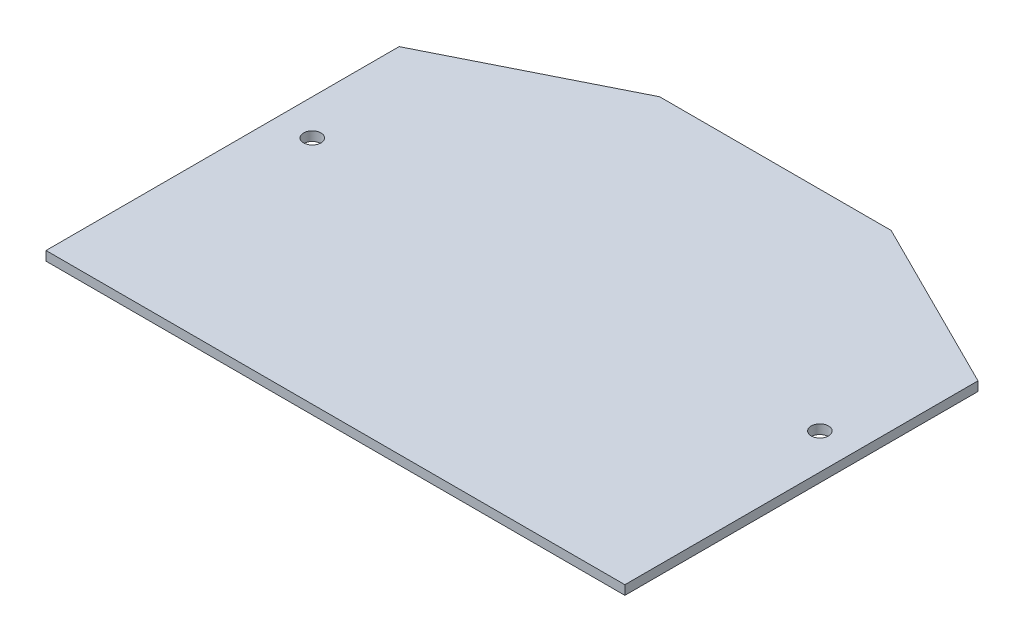
SolidWorks part; units mm, degrees
ref_plane "Front Plane" through (0, 0, 0) normal (0, 0, 1) x (1, 0, 0)
ref_plane "Top Plane" through (0, 0, 0) normal (0, 1, 0) x (1, 0, 0)
ref_plane "Right Plane" through (0, 0, 0) normal (1, 0, 0) x (0, 0, -1)
sketch "Sketch1" plane through (0, 0, 0) normal (0, 1, 0) x (1, 0, 0)
  line L0 (-50, 65) -> (-20, 80)
  line L1 (-50, 4) -> (-50, 65)
  line L3 (-20, 80) -> (0, 80)
  line L4 (0, 4) -> (0, 80)
  line L5 (0, 4) -> (-50, 4)
  line L6 (-59.397, 28.2843) -> (-43.8406, 43.8406) construction
  line L7 (-51.9976, -33.7676) -> (-63.9796, -15.3169) construction
  line L9 (0, 0) -> (-85, 0) construction
  line L10 (-43.8406, 43.8406) -> (0, 0) construction
  line L11 (-51.9976, -33.7676) -> (0, 0) construction
  circle A0 centre (0, 0) radius 85 construction
  circle A1 centre (-43.8406, 43.8406) radius 1.5
  circle A4 centre (-63.9796, -15.3169) radius 1.5 construction
  dimension "D7" = 3
  dimension "D17" = 170
  dimension "D2" = 76
  dimension "D3" = 30
  dimension "D4" = 15
  dimension "D5" = 80
  dimension "D6" = 50
  dimension "D8" = 62
  dimension "D9" = 22
  dimension "D10" = 22
  dimension "D11" = 6.1594
  dimension "D12" = 36.1594
  dimension "D14" = 45
  dimension "D15" = 33
extrude "Boss-Extrude1" add sketch "Sketch1" along normal blind 1.6
mirror "Mirror1" about plane through (0, 1.6, -4) normal (-1, 0, 0) of "Boss-Extrude1"
